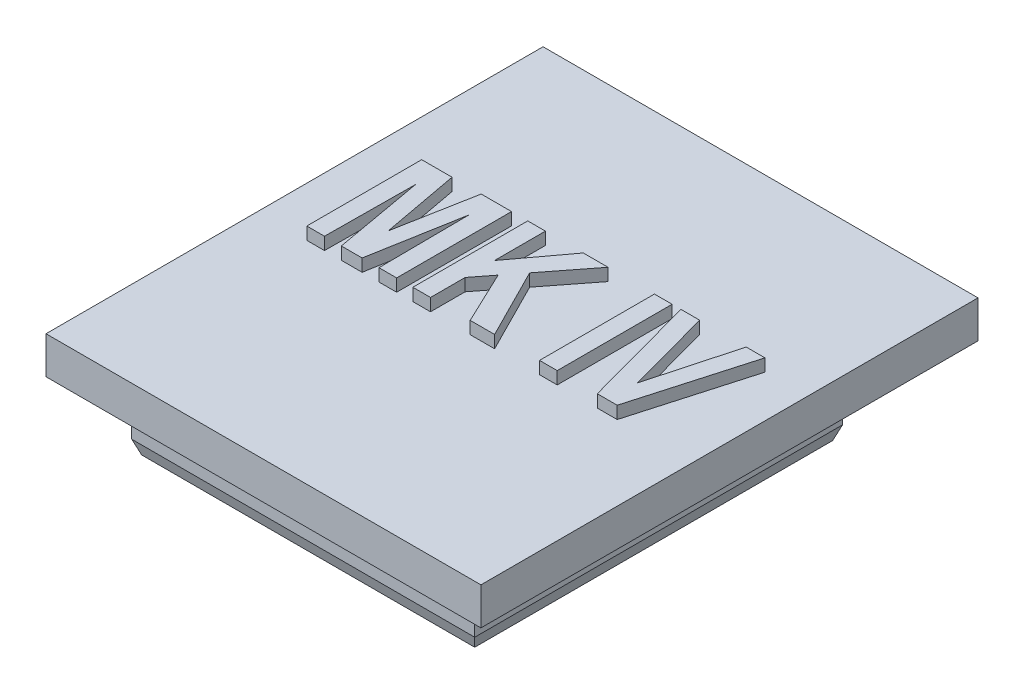
SolidWorks part; units mm, degrees
ref_plane "Спереди" through (0, 0, 0) normal (0, 0, 1) x (1, 0, 0)
ref_plane "Сверху" through (0, 0, 0) normal (0, 1, 0) x (1, 0, 0)
ref_plane "Справа" through (0, 0, 0) normal (1, 0, 0) x (0, 0, -1)
sketch "Sketch1" plane through (0, 0, 0) normal (0, 1, 0) x (1, 0, 0)
  line L1 (13.8, -14.8) -> (-13.8, -14.8)
  line L2 (13.8, -14.8) -> (13.8, 14.8)
  line L3 (13.8, 14.8) -> (-13.8, 14.8)
  line L4 (-13.8, -14.8) -> (-13.8, 14.8)
  line L5 (13.8, -14.8) -> (-13.8, 14.8) construction
  line L6 (13.8, 14.8) -> (-13.8, -14.8) construction
  point P0 (0, 0)
  dimension "D1" = 27.6
  dimension "D2" = 29.6
extrude "Boss-Extrude1" add sketch "Sketch1" along normal blind 4
sketch "Sketch2" plane through (0, 4, 0) normal (0, 1, 0) x (1, 0, 0)
  line L0 (-1.2, 14.8) -> (-1.2, -14.8) construction
  line L1 (13.8, 14.8) -> (-13.8, 14.8) construction
  line L2 (-13.8, -14.8) -> (13.8, -14.8) construction
  line L3 (-13.8, 3.2) -> (13.8, 3.2) construction
  line L4 (-13.8, 14.8) -> (-13.8, -14.8) construction
  line L5 (13.8, -14.8) -> (13.8, 14.8) construction
  line L7 (16.3, -16.8) -> (-18.7, -16.8)
  line L8 (16.3, -16.8) -> (16.3, 23.2)
  line L9 (16.3, 23.2) -> (-18.7, 23.2)
  line L10 (-18.7, -16.8) -> (-18.7, 23.2)
  line L11 (16.3, -16.8) -> (-18.7, 23.2) construction
  line L12 (16.3, 23.2) -> (-18.7, -16.8) construction
  point P12 (-1.2, 3.2)
  dimension "D1" = 35
  dimension "D2" = 40
  dimension "D3" = 18
  dimension "D4" = 15
extrude "Boss-Extrude2" add sketch "Sketch2" along normal blind 3
chamfer "Chamfer1" distance 0.4 angle 70 4 edges at (0, 0, 14.8) (13.8, 0, 0) (0, 0, -14.8) (-13.8, 0, 0) first distance on face at (0, 0, 0)
sketch "Sketch3" plane through (0, 7, 0) normal (0, 1, 0) x (1, 0, 0)
  line L0 (-18.7, 0.2) -> (16.3, 0.2) construction
  line L1 (-18.7, 23.2) -> (-18.7, -16.8) construction
  line L2 (16.3, -16.8) -> (16.3, 23.2) construction
  line L3 (-18.7, -16.8) -> (16.3, -16.8) construction
  text T0 "<b>MK IV</b>" font "Arial" height in points 36
  point P7 (-18.7, 3.2)
  point P8 (-16.9508, -2.0804)
  dimension "D1" = 17
extrude "Boss-Extrude3" add sketch "Sketch3" along normal blind 1
